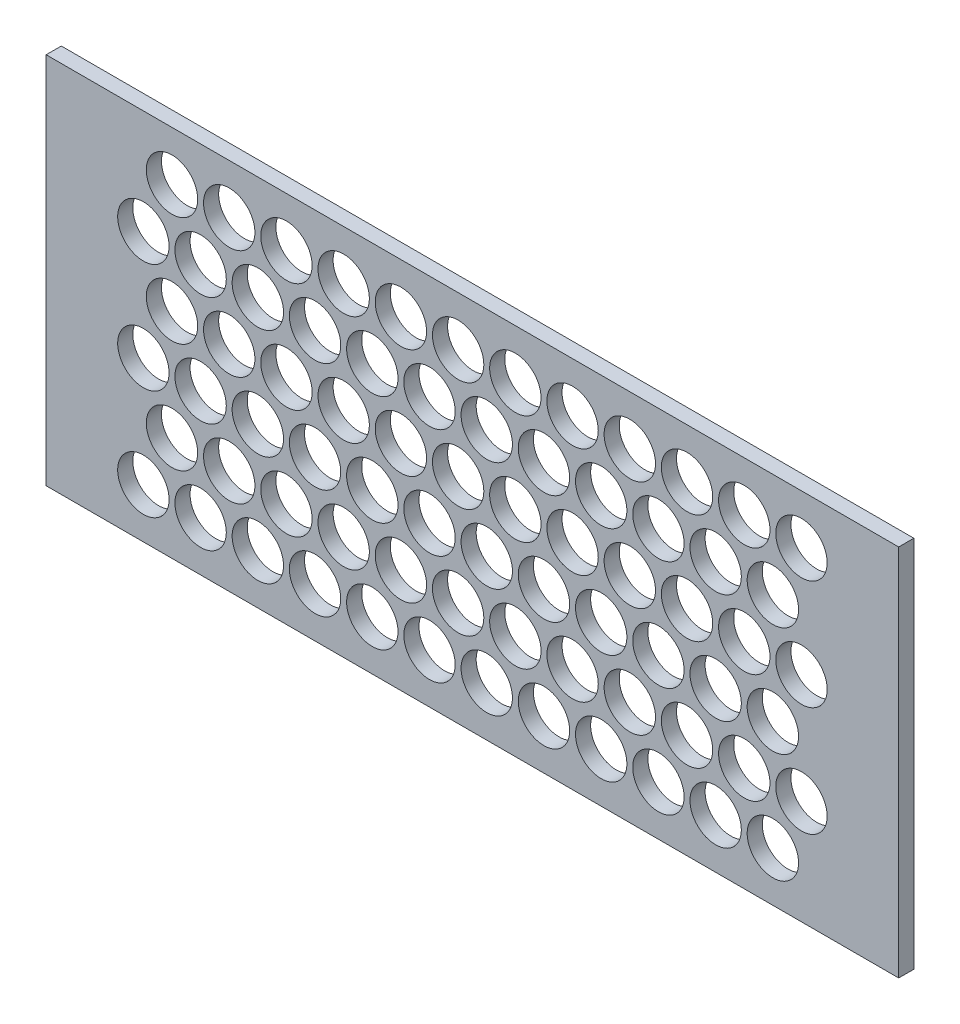
SolidWorks part; units mm, degrees
material "Custom Plastic"
ref_plane "X-Y Datum" through (0, 0, 0) normal (0, 0, 1) x (1, 0, 0)
ref_plane "X-Z Datum" through (0, 0, 0) normal (0, 1, 0) x (1, 0, 0)
ref_plane "Y-Z Datum" through (0, 0, 0) normal (1, 0, 0) x (0, 0, -1)
sketch "Sketch1" plane through (0, 0, 0) normal (0, 0, 1) x (1, 0, 0)
  line L0 (-158.775, 78.275) -> (-158.775, -78.275)
  line L1 (-148.775, 68.275) -> (148.775, 68.275)
  line L2 (-148.775, 68.275) -> (-148.775, -68.275)
  line L3 (-148.775, -68.275) -> (148.775, -68.275)
  line L4 (148.775, 68.275) -> (148.775, -68.275)
  line L5 (-148.775, 68.275) -> (148.775, -68.275) construction
  line L6 (-148.775, -68.275) -> (148.775, 68.275) construction
  line L7 (-158.775, -78.275) -> (158.775, -78.275)
  line L8 (158.775, 78.275) -> (158.775, -78.275)
  line L9 (-158.775, 78.275) -> (158.775, 78.275)
  line L10 (178.775, 78.275) -> (178.775, -78.275)
  line L11 (178.775, -78.275) -> (158.775, -78.275)
  line L12 (178.775, 78.275) -> (158.775, 78.275)
  line L13 (-178.775, 78.275) -> (-178.775, -78.275)
  line L14 (-178.775, 78.275) -> (-158.775, 78.275)
  line L15 (-158.775, -78.275) -> (-178.775, -78.275)
  circle A0 centre (-138, -57.5) radius 10.775
  circle A1 centre (-114, -57.5) radius 10.775 construction
  circle A2 centre (-126, -34.5) radius 10.775
  point P0 (0, 0)
  dimension "D1" = 21.55
  dimension "D2" = 24
  dimension "D3" = 23
  dimension "D4" = 12
  dimension "D5" = 136.55
  dimension "D6" = 297.55
  dimension "D7" = 10
  dimension "D8" = 20
  dimension "D9" = 20
extrude "Boss-Extrude1" add sketch "Sketch1" along normal blind 6.35 contours A0 L3 L4 L1 L2 A2 | A2 | A0 | A0 L2 L3 | L9 L0 L7 L8 L1 L4 L3 L2 | L10 L12 L8 L11 | L15 L0 L14 L13 region at (0, 74.7346, 0) region at (-168.775, 0, 0) region at (168.775, 0, 0) region at (2.5062, 0.8827, 0) region at (-146.3682, -65.8682, 0) region at (-138, -57.5, 0) region at (-126, -34.5, 0)
sketch "Sketch3" plane through (0, 0, 6.35) normal (0, 0, 1) x (1, 0, 0)
  line L4 (148.775, 68.275) -> (-148.775, 68.275)
  line L5 (148.775, -68.275) -> (148.775, 68.275)
  line L6 (-148.775, -68.275) -> (148.775, -68.275)
  line L7 (-148.775, 68.275) -> (-148.775, -68.275)
  line L8 (148.775, 68.275) -> (-148.775, 68.275)
  line L9 (148.775, -68.275) -> (148.775, 68.275)
  line L10 (-148.775, -68.275) -> (148.775, -68.275)
  line L11 (-148.775, 68.275) -> (-148.775, -68.275)
  line L12 (158.775, 78.275) -> (158.775, -78.275)
  line L16 (158.775, 78.275) -> (158.775, -78.275)
  circle A1 centre (-126, -34.5) radius 10.775
  circle A2 centre (-126, -34.5) radius 10.775
  circle A3 centre (-138, -57.5) radius 10.775
  circle A4 centre (-138, -57.5) radius 10.775
  dimension "D1" = 0
  dimension "D2" = 0
  dimension "D3" = 0
  dimension "D4" = 0
extrude "Cut-Extrude1" cut sketch "Sketch3" against normal through all contours A4 region at (-138, -57.5, 6.35)
sketch "Sketch4" plane through (0, 0, 6.35) normal (0, 0, 1) x (1, 0, 0)
  line L4 (148.775, 68.275) -> (-148.775, 68.275)
  line L5 (148.775, -68.275) -> (148.775, 68.275)
  line L6 (-148.775, -68.275) -> (148.775, -68.275)
  line L7 (-148.775, 68.275) -> (-148.775, -68.275)
  line L8 (148.775, 68.275) -> (-148.775, 68.275)
  line L9 (148.775, -68.275) -> (148.775, 68.275)
  line L10 (-148.775, -68.275) -> (148.775, -68.275)
  line L11 (-148.775, 68.275) -> (-148.775, -68.275)
  line L12 (158.775, 78.275) -> (158.775, -78.275)
  line L16 (158.775, 78.275) -> (158.775, -78.275)
  circle A1 centre (-126, -34.5) radius 10.775
  circle A2 centre (-126, -34.5) radius 10.775
  circle A3 centre (-138, -57.5) radius 10.775
  circle A4 centre (-138, -57.5) radius 10.775
  dimension "D1" = 0
  dimension "D2" = 0
  dimension "D3" = 0
  dimension "D4" = 0
extrude "Cut-Extrude2" cut sketch "Sketch4" against normal through all contours A2 region at (-126, -34.5, 6.35)
pattern_linear "LPattern1" count 12 spacing 24 along (1, 0, 0) of "Cut-Extrude1", "Cut-Extrude2"
pattern_linear "LPattern2" count 3 spacing 46 along (0, 1, 0) of "LPattern1"
